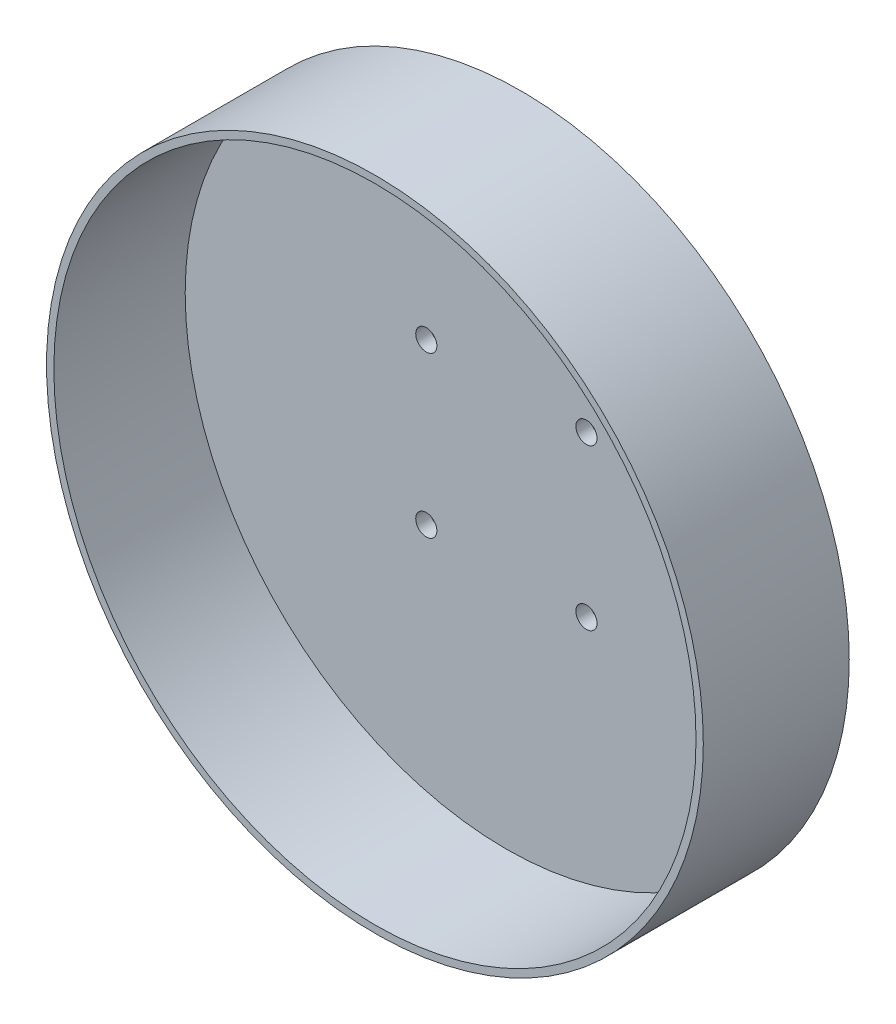
SolidWorks part; units mm, degrees
note: The reader was unsure of these and kept them because the rebuilt part matched: shared geometry of "Sketch1<2>".
ref_plane "Front Plane" through (0, 0, 0) normal (0, 0, 1) x (1, 0, 0)
ref_plane "Top Plane" through (0, 0, 0) normal (0, 1, 0) x (1, 0, 0)
ref_plane "Right Plane" through (0, 0, 0) normal (1, 0, 0) x (0, 0, -1)
sketch "Sketch1" plane through (0, 0, 0) normal (0, 0, 1) x (1, 0, 0)
  circle A0 centre (0, 0) radius 45
  circle A1 centre (0, 0) radius 44
  dimension "D1" = 90
  dimension "D2" = 88
extrude "Boss-Extrude1" add sketch "Sketch1" along normal blind 18
extrude "Boss-Extrude2" add sketch "Sketch1<2>" against normal blind 2 contours A1 | A0 A1
sketch "Sketch1<2>" plane through (0, 0, 0) normal (0, 0, 1) x (1, 0, 0) same geometry as "Sketch1"
sketch "Sketch2" plane through (0, 0, -2) normal (0, 0, -1) x (-1, 0, 0)
  line L0 (0, 0) -> (15.5, 0) construction
  line L1 (0, 0) -> (10.9602, 10.9602) construction
  circle A0 centre (0, 0) radius 15.5 construction
  dimension "D1" = 31
  dimension "D2" = 45
hole_wizard "M3.5x0.6 Tapped Hole1" positions "Sketch3" profile "Sketch4" tap size "M3.5x0.6" standard "ANSI Metric" end condition through all
sketch "Sketch3" plane through (0, 0, -2) normal (0, 0, -1) x (-1, 0, 0)
  point P0 (10.9602, 10.9602)
sketch "Sketch4" plane through (-10.9602, 10.9602, -2) normal (1, 0, 0) x (0, 1, 0)
  line L0 (0, 0) -> (0, 20)
  line L1 (0, 20) -> (1.45, 20)
  line L2 (1.45, 20) -> (1.45, 0)
  line L5 (1.45, 0) -> (0, 0)
  line L11 (0, -6.35) -> (0, 107.95) construction
  dimension "Thru Tap Drill Dia." = 2.9
  dimension "Thru Tap Drill Depth" = 20
cosmetic thread "Hole Thread1"
pattern_circular "CirPattern1" count 4 over 360 about axis through (0.0114, -0.0114, 0) along (0, 0, 1) of "M3.5x0.6 Tapped Hole1"
cosmetic thread "Hole Thread2"
cosmetic thread "Hole Thread3"
cosmetic thread "Hole Thread4"
